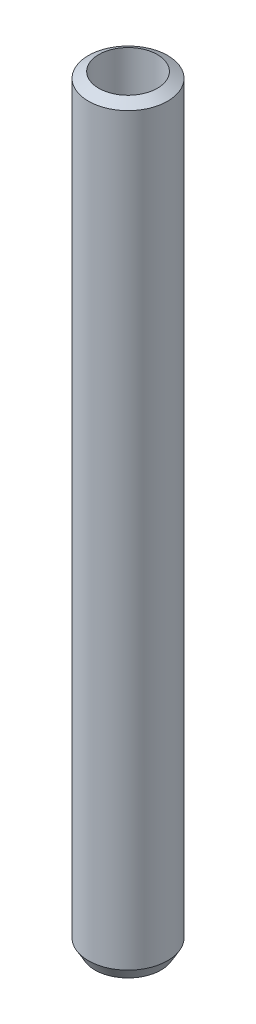
SolidWorks part; units mm, degrees
ref_plane "Front Plane" through (0, 0, 0) normal (0, 0, 1) x (1, 0, 0)
ref_plane "Top Plane" through (0, 0, 0) normal (0, 1, 0) x (1, 0, 0)
ref_plane "Right Plane" through (0, 0, 0) normal (1, 0, 0) x (0, 0, -1)
sketch "Sketch1" plane through (0, 0, 0) normal (0, 1, 0) x (1, 0, 0)
  circle A0 centre (0, 0) radius 20
  dimension "SHAFT_OD" = 40
extrude "Boss-Extrude1" add sketch "Sketch1" along normal blind 384.8464
sketch "Sketch2" plane through (0, 0, 0) normal (0, 1, 0) x (1, 0, 0)
  circle A0 centre (0, 0) radius 14.7746
  dimension "BORE_D" = 29.5492
extrude "Cut-Extrude1" cut sketch "Sketch2" along normal through all
chamfer "Chamfer1" distance 3.3449 angle 60 2 edges at (0, 384.8464, 20) (0, 0, 20) first distance on face at (0, 384.8464, 20) first distance on face at (0, 0, 14.7746)
